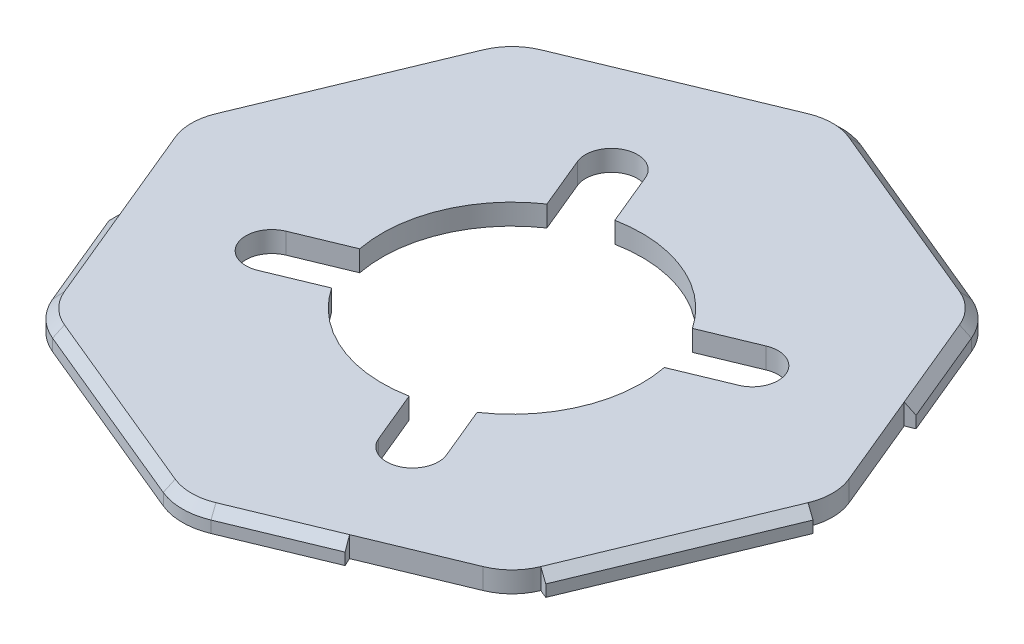
SolidWorks part; units mm, degrees
ref_plane "Front Plane" through (0, 0, 0) normal (0, 0, 1) x (1, 0, 0)
ref_plane "Top Plane" through (0, 0, 0) normal (0, 1, 0) x (1, 0, 0)
ref_plane "Right Plane" through (0, 0, 0) normal (1, 0, 0) x (0, 0, -1)
sketch "Sketch1" plane through (0, 0, 0) normal (0, 1, 0) x (1, 0, 0)
  line L0 (-9.3375, -22.5427) -> (-2.0665, -25.5544) construction
  line L1 (2.0665, -25.5544) -> (16.6085, -19.5309) construction
  line L2 (19.5309, -16.6085) -> (25.5544, -2.0665) construction
  line L3 (25.5544, 2.0665) -> (19.5309, 16.6085) construction
  line L4 (16.6085, 19.5309) -> (2.0665, 25.5544) construction
  line L5 (-2.0665, 25.5544) -> (-16.6085, 19.5309) construction
  line L6 (-19.5309, 16.6085) -> (-25.5544, 2.0665) construction
  line L7 (-25.5544, -2.0665) -> (-19.5309, -16.6085) construction
  line L8 (-16.6085, -19.5309) -> (-9.3375, -22.5427) construction
  line L9 (-9.1079, -21.9883) -> (-1.8369, -25.0001)
  line L10 (1.8369, -25.0001) -> (16.3789, -18.9766)
  line L11 (18.9766, -16.3789) -> (25.0001, -1.8369)
  line L12 (25.0001, 1.8369) -> (18.9766, 16.3789)
  line L13 (16.3789, 18.9766) -> (1.8369, 25.0001)
  line L14 (-1.8369, 25.0001) -> (-16.3789, 18.9766)
  line L15 (-18.9766, 16.3789) -> (-25.0001, 1.8369)
  line L16 (-25.0001, -1.8369) -> (-18.9766, -16.3789)
  line L17 (-16.3789, -18.9766) -> (-9.1079, -21.9883)
  arc A0 (-2.0665, -25.5544) -> (2.0665, -25.5544) centre (0, -20.5655) ccw construction
  arc A1 (16.6085, -19.5309) -> (19.5309, -16.6085) centre (14.542, -14.542) ccw construction
  arc A2 (25.5544, -2.0665) -> (25.5544, 2.0665) centre (20.5655, 0) ccw construction
  arc A3 (19.5309, 16.6085) -> (16.6085, 19.5309) centre (14.542, 14.542) ccw construction
  arc A4 (2.0665, 25.5544) -> (-2.0665, 25.5544) centre (0, 20.5655) ccw construction
  arc A5 (-16.6085, 19.5309) -> (-19.5309, 16.6085) centre (-14.542, 14.542) ccw construction
  arc A6 (-25.5544, 2.0665) -> (-25.5544, -2.0665) centre (-20.5655, 0) ccw construction
  arc A7 (-19.5309, -16.6085) -> (-16.6085, -19.5309) centre (-14.542, -14.542) ccw construction
  arc A8 (-1.8369, -25.0001) -> (1.8369, -25.0001) centre (0, -20.5655) ccw
  arc A9 (16.3789, -18.9766) -> (18.9766, -16.3789) centre (14.542, -14.542) ccw
  arc A10 (25.0001, -1.8369) -> (25.0001, 1.8369) centre (20.5655, 0) ccw
  arc A11 (18.9766, 16.3789) -> (16.3789, 18.9766) centre (14.542, 14.542) ccw
  arc A12 (1.8369, 25.0001) -> (-1.8369, 25.0001) centre (0, 20.5655) ccw
  arc A13 (-16.3789, 18.9766) -> (-18.9766, 16.3789) centre (-14.542, 14.542) ccw
  arc A14 (-25.0001, 1.8369) -> (-25.0001, -1.8369) centre (-20.5655, 0) ccw
  arc A15 (-18.9766, -16.3789) -> (-16.3789, -18.9766) centre (-14.542, -14.542) ccw
  dimension "D1" = 0.6
extrude "Boss-Extrude1" add sketch "Sketch1" along normal blind 1.6
chamfer "Chamfer1" distance 0.7 angle 45 16 edges at (25.3655, 1.6, 0) (21.9883, 1.6, 9.1079) (17.9361, 1.6, 17.9361) (9.1079, 1.6, 21.9883) (0, 1.6, 25.3655) (-9.1079, 1.6, 21.9883) (-17.9361, 1.6, 17.9361) (-21.9883, 1.6, 9.1079) (-25.3655, 1.6, 0) (-21.9883, 1.6, -9.1079) (-17.9361, 1.6, -17.9361) (-9.1079, 1.6, -21.9883) (0, 1.6, -25.3655) (9.1079, 1.6, -21.9883) (17.9361, 1.6, -17.9361) (21.9883, 1.6, -9.1079)
sketch "Sketch3" plane through (0, 1.6, 0) normal (0, 1, 0) x (1, 0, 0)
  line L0 (-24.3534, -1.569) -> (-18.3299, -16.111) construction
  line L1 (1.569, -24.3534) -> (16.111, -18.3299) construction
  line L2 (11.1843, -26.4004) -> (8.84, -21.3416)
  line L3 (24.3534, 1.569) -> (18.3299, 16.111) construction
  line L4 (-1.569, 24.3534) -> (-16.111, 18.3299) construction
  line L6 (8.84, -21.3416) -> (16.111, -18.3299)
  line L8 (24.3534, 1.569) -> (21.3416, 8.84)
  line L9 (-8.84, 21.3416) -> (-16.111, 18.3299)
  line L11 (-24.3534, -1.569) -> (-21.3416, -8.84)
  line L12 (-8.84, 21.3416) -> (-9.7472, 23.5317)
  line L13 (21.3416, 8.84) -> (23.9462, 9.9189)
  line L16 (11.1843, -26.4004) -> (36.794, -9.1023)
  line L17 (36.794, -9.1023) -> (23.9462, 9.9189)
  line L18 (-21.3416, -8.84) -> (-32.211, -10.9863)
  line L20 (-32.211, -10.9863) -> (-37.9282, 17.9671)
  line L21 (-37.9282, 17.9671) -> (-9.7472, 23.5317)
  line L22 (-24.3534, 1.569) -> (-26.1536, 2.3147)
  line L23 (-18.3299, 16.111) -> (-20.5655, 17.037)
  line L24 (-26.1536, 2.3147) -> (-20.5655, 17.037)
  line L25 (18.3299, -16.111) -> (20.5655, -17.037)
  line L26 (24.3534, -1.569) -> (27.4828, -2.8652)
  line L27 (20.5655, -17.037) -> (27.4828, -2.8652)
  arc A2 (16.111, -18.3299) -> (18.3299, -16.111) centre (14.542, -14.542) ccw construction
  arc A3 (24.3534, -1.569) -> (24.3534, 1.569) centre (20.5655, 0) ccw construction
  arc A4 (-16.111, 18.3299) -> (-18.3299, 16.111) centre (-14.542, 14.542) ccw construction
  arc A5 (-24.3534, 1.569) -> (-24.3534, -1.569) centre (-20.5655, 0) ccw construction
  arc A6 (16.111, -18.3299) -> (18.3299, -16.111) centre (14.542, -14.542) ccw
  arc A7 (24.3534, -1.569) -> (24.3534, 1.569) centre (20.5655, 0) ccw
  arc A8 (-16.111, 18.3299) -> (-18.3299, 16.111) centre (-14.542, 14.542) ccw
  arc A9 (-24.3534, 1.569) -> (-24.3534, -1.569) centre (-20.5655, 0) ccw
  point P0 (11.1843, -26.4004)
extrude "Cut-Extrude1" cut sketch "Sketch3" against normal blind 10
sketch "Sketch4" plane through (0, 1.6, 0) normal (0, 1, 0) x (1, 0, 0)
  line L0 (-16.111, -18.3299) -> (-1.569, -24.3534) construction
  line L1 (-5.412, 13.0656) -> (13.0656, 5.412) construction
  line L2 (-5.412, 13.0656) -> (-13.0656, -5.412) construction
  line L3 (-13.0656, -5.412) -> (5.412, -13.0656) construction
  line L4 (13.0656, 5.412) -> (5.412, -13.0656) construction
  line L5 (-5.412, 13.0656) -> (5.412, -13.0656) construction
  line L6 (-13.0656, -5.412) -> (13.0656, 5.412) construction
  line L7 (-7.2597, 12.3003) -> (-5.5973, 8.2868)
  line L8 (-3.5642, 13.831) -> (-1.9018, 9.8175)
  line L9 (-13.831, -3.5642) -> (-9.8175, -1.9018)
  line L10 (-12.2996, -7.2594) -> (-8.2876, -5.596)
  line L11 (1.9018, -9.8175) -> (3.5642, -13.831)
  line L12 (8.2868, 5.5973) -> (12.3003, 7.2597)
  line L13 (5.5973, -8.2868) -> (7.2597, -12.3003)
  line L14 (9.8159, 1.9102) -> (14.0122, 3.6501)
  arc A0 (-8.2876, -5.596) -> (1.9018, -9.8175) centre (0, 0) ccw
  arc A1 (-3.5642, 13.831) -> (-7.2597, 12.3003) centre (-5.412, 13.0656) ccw
  arc A2 (14.0122, 3.6501) -> (12.3003, 7.2597) centre (13.0656, 5.412) ccw
  arc A3 (3.5642, -13.831) -> (7.2597, -12.3003) centre (5.412, -13.0656) ccw
  arc A4 (-13.831, -3.5642) -> (-12.2996, -7.2594) centre (-13.0656, -5.412) ccw
  arc A5 (5.5973, -8.2868) -> (9.8159, 1.9102) centre (0, 0) ccw
  arc A6 (8.2868, 5.5973) -> (-1.9018, 9.8175) centre (0, 0) ccw
  arc A7 (-5.5973, 8.2868) -> (-9.8175, -1.9018) centre (0, 0) ccw
  point P9 (0, 0)
  point P10 (0, 0)
  point P11 (0, 0)
  dimension "D1" = 20
  dimension "D4" = 4
  dimension "D2" = 20
  dimension "D3" = 20
extrude "Cut-Extrude2" cut sketch "Sketch4" against normal blind 10
ref_axis "Axis1" through (0, 0, 0) along (0, 1, 0)
ref_point "Point1"
